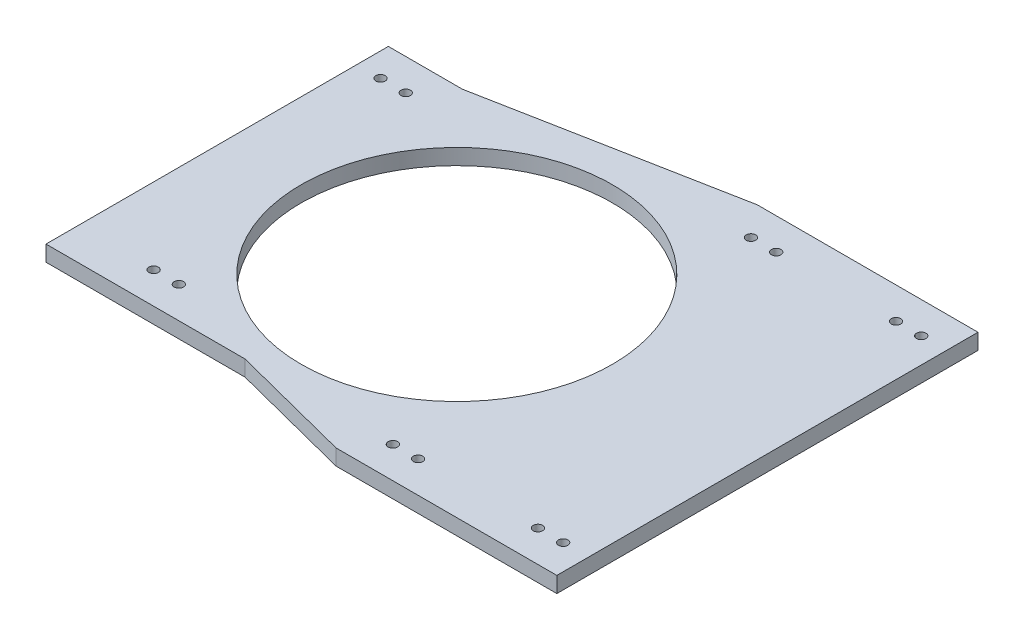
SolidWorks part; units mm, degrees
ref_plane "Front Plane" through (0, 0, 0) normal (0, 0, 1) x (1, 0, 0)
ref_plane "Top Plane" through (0, 0, 0) normal (0, 1, 0) x (1, 0, 0)
ref_plane "Right Plane" through (0, 0, 0) normal (1, 0, 0) x (0, 0, -1)
sketch "Sketch1" plane through (0, 0, 0) normal (0, 1, 0) x (1, 0, 0)
  line L1 (131.445, -84.8119) -> (-131.445, -84.8119)
  line L2 (131.445, -84.8119) -> (131.445, 84.8119)
  line L3 (131.445, 84.8119) -> (-131.445, 84.8119)
  line L4 (-131.445, -84.8119) -> (-131.445, 84.8119)
  line L5 (131.445, -84.8119) -> (-131.445, 84.8119) construction
  line L6 (131.445, 84.8119) -> (-131.445, -84.8119) construction
  circle A0 centre (6.35, 0) radius 62.6745
  point P0 (0, 0)
  dimension "D3" = 125.349
  dimension "D4" = 6.35
  dimension "D1" = 262.89
  dimension "D2" = 169.6237
extrude "Boss-Extrude1" add sketch "Sketch1" along normal blind 6.35
sketch "Sketch2" plane through (0, 0, 0) normal (0, -1, 0) x (1, 0, 0)
  line L0 (-131.445, 84.8119) -> (131.445, 84.8119) construction
  line L6 (-131.445, -84.8119) -> (-86.995, -84.8119)
  line L7 (-131.445, -84.8119) -> (-131.445, 84.8119)
  line L8 (-131.445, 84.8119) -> (-86.995, 84.8119)
  line L9 (-86.995, -84.8119) -> (-86.995, 84.8119)
  dimension "D2" = 44.45
extrude "Cut-Extrude1" cut sketch "Sketch2" against normal through all
sketch "Sketch3" plane through (0, 0, 0) normal (0, -1, 0) x (1, 0, 0)
  line L0 (42.545, -84.8119) -> (-57.117, -65.7619)
  line L3 (131.445, -84.8119) -> (-86.995, -84.8119) construction
  line L5 (-57.117, -65.7619) -> (-86.995, -65.7619)
  line L6 (-86.995, -84.8119) -> (-86.995, 84.8119) construction
  line L7 (42.545, 84.8119) -> (-6.825, 72.1119)
  line L8 (-86.995, 84.8119) -> (131.445, 84.8119) construction
  line L9 (-6.825, 72.1119) -> (-86.995, 72.1119)
  line L10 (-86.995, 72.1119) -> (-86.995, 84.8119)
  line L11 (-86.995, 84.8119) -> (42.545, 84.8119)
  line L12 (42.545, -84.8119) -> (-86.995, -84.8119)
  line L13 (-86.995, -84.8119) -> (-86.995, -65.7619)
  dimension "D1" = 19.05
  dimension "D2" = 12.7
  dimension "D3" = 129.54
  dimension "D4" = 129.54
  dimension "D5" = 29.878
  dimension "D6" = 80.17
extrude "Cut-Extrude2" cut sketch "Sketch3" against normal through all
hole_wizard "#6 Clearance Hole1" positions "Sketch4" profile "Sketch5" hole size "#6" standard "ANSI Inch" end condition through all
sketch "Sketch4" plane through (0, 0, 0) normal (0, -1, 0) x (-1, 0, 0)
  line L0 (-121.285, 72.1119) -> (-111.125, 72.1119)
  line L2 (-62.865, 72.1119) -> (-52.705, 72.1119)
  line L4 (-131.445, 84.8119) -> (-42.545, 84.8119) construction
  line L5 (-131.445, -84.8119) -> (-131.445, 84.8119) construction
  point P0 (-121.285, 72.1119)
  point P2 (-111.125, 72.1119)
  point P4 (-62.865, 72.1119)
  point P6 (-52.705, 72.1119)
  dimension "D1" = 12.7
  dimension "D2" = 12.7
  dimension "D3" = 10.16
  dimension "D4" = 10.16
  dimension "D5" = 10.16
  dimension "D6" = 10.16
sketch "Sketch5" plane through (121.285, 0, -72.1119) normal (1, 0, 0) x (0, 0, -1)
  line L0 (0, 0) -> (0, 6.35)
  line L1 (0, 6.35) -> (1.8986, 6.35)
  line L2 (1.8986, 6.35) -> (1.8986, 0)
  line L5 (1.8986, 0) -> (0, 0)
  line L11 (0, -6.35) -> (0, 107.95) construction
  dimension "Thru Hole Dia." = 3.7973
  dimension "Thru Hole Depth" = 6.35
mirror "Mirror1" about plane through (0, 0, 0) normal (0, 0, 1) of "#6 Clearance Hole1"
hole_wizard "#6 Clearance Hole2" positions "Sketch6" profile "Sketch7" hole size "#6" standard "ANSI Inch" end condition through all
sketch "Sketch6" plane through (0, 6.35, 0) normal (0, 1, 0) x (1, 0, 0)
  line L0 (-77.437, 53.0619) -> (-67.277, 53.0619)
  line L2 (-57.117, 65.7619) -> (-86.995, 65.7619) construction
  point P0 (-67.277, 53.0619)
  point P2 (-77.437, 53.0619)
  dimension "D1" = 10.16
  dimension "D2" = 12.7
  dimension "D3" = 10.16
sketch "Sketch7" plane through (-67.277, 6.35, -53.0619) normal (1, 0, 0) x (0, 0, 1)
  line L0 (0, 0) -> (0, 6.35)
  line L1 (0, 6.35) -> (1.8986, 6.35)
  line L2 (1.8986, 6.35) -> (1.8986, 0)
  line L5 (1.8986, 0) -> (0, 0)
  line L11 (0, -6.35) -> (0, 107.95) construction
  dimension "Thru Hole Dia." = 3.7973
  dimension "Thru Hole Depth" = 6.35
hole_wizard "#6 Clearance Hole3" positions "Sketch8" profile "Sketch9" hole size "#6" standard "ANSI Inch" end condition through all
sketch "Sketch8" plane through (0, 6.35, 0) normal (0, 1, 0) x (1, 0, 0)
  line L0 (-56.355, -59.4119) -> (-46.195, -59.4119)
  line L2 (-86.995, -72.1119) -> (-6.825, -72.1119) construction
  point P0 (-46.195, -59.4119)
  point P2 (-56.355, -59.4119)
  dimension "D1" = 10.16
  dimension "D2" = 39.37
  dimension "D3" = 12.7
sketch "Sketch9" plane through (-46.195, 6.35, 59.4119) normal (1, 0, 0) x (0, 0, 1)
  line L0 (0, 0) -> (0, 6.35)
  line L1 (0, 6.35) -> (1.8986, 6.35)
  line L2 (1.8986, 6.35) -> (1.8986, 0)
  line L5 (1.8986, 0) -> (0, 0)
  line L11 (0, -6.35) -> (0, 107.95) construction
  dimension "Thru Hole Dia." = 3.7973
  dimension "Thru Hole Depth" = 6.35
